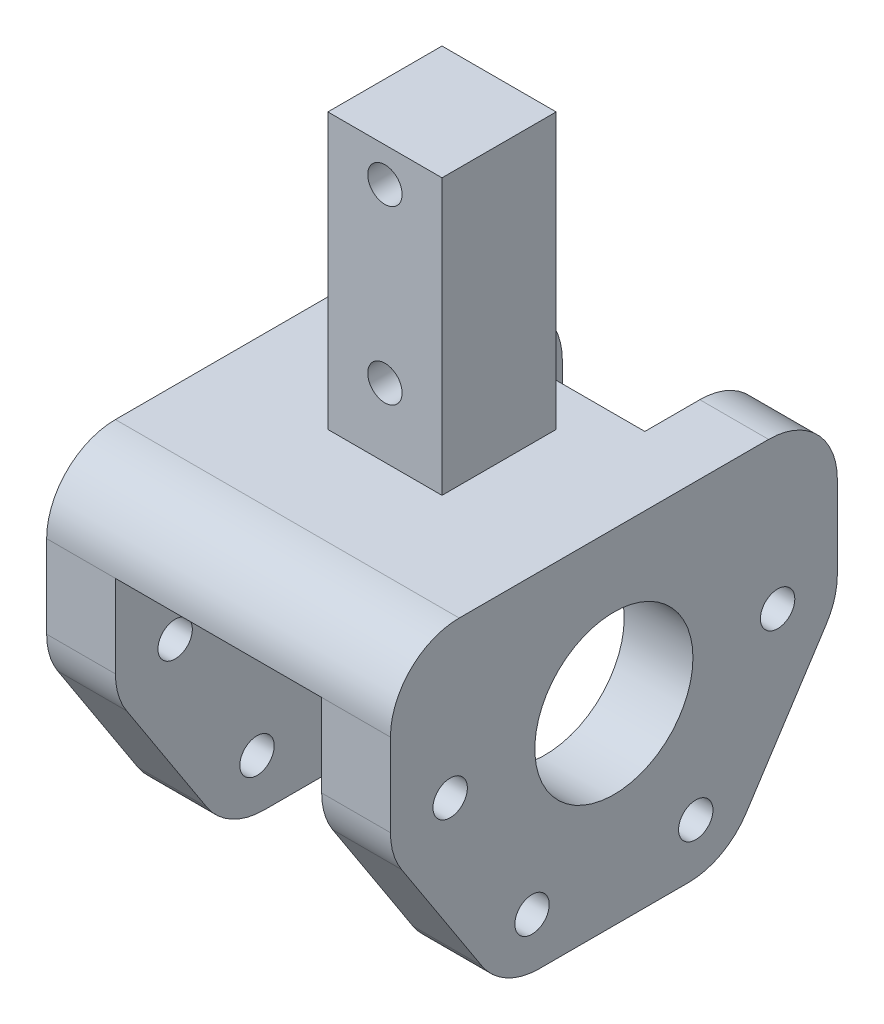
SolidWorks part; units mm, degrees
material "Nylon - impressão"
ref_plane "Plano frontal" through (0, 0, 0) normal (0, 0, 1) x (1, 0, 0)
ref_plane "Plano superior" through (0, 0, 0) normal (0, 1, 0) x (1, 0, 0)
ref_plane "Plano direito" through (0, 0, 0) normal (1, 0, 0) x (0, 0, -1)
sketch "Esboço1" plane through (0, 0, 0) normal (0, 1, 0) x (1, 0, 0)
  line L1 (-8.3, -8.3) -> (8.3, -8.3)
  line L2 (-8.3, -8.3) -> (-8.3, 8.3)
  line L3 (-8.3, 8.3) -> (8.3, 8.3)
  line L4 (8.3, -8.3) -> (8.3, 8.3)
  line L5 (-8.3, -8.3) -> (8.3, 8.3) construction
  line L6 (-8.3, 8.3) -> (8.3, -8.3) construction
  point P0 (0, 0)
  dimension "D1" = 16.6
extrude "Ressalto-extrusão1" add sketch "Esboço1" along normal blind 40
sketch "Esboço2" plane through (0, 0, 0) normal (0, -1, 0) x (1, 0, 0)
  line L1 (-25, -32.5) -> (25, -32.5)
  line L2 (-25, -32.5) -> (-25, 32.5)
  line L3 (-25, 32.5) -> (25, 32.5)
  line L4 (25, -32.5) -> (25, 32.5)
  line L5 (-25, -32.5) -> (25, 32.5) construction
  line L6 (-25, 32.5) -> (25, -32.5) construction
  point P0 (0, 0)
  dimension "D1" = 65
  dimension "D2" = 50
extrude "Ressalto-extrusão2" add sketch "Esboço2" along normal blind 50
sketch "Esboço3" plane through (0, 0, 32.5) normal (0, 0, 1) x (1, 0, 0)
  line L0 (25, -50) -> (-25, -50) construction
  line L1 (-15, -50) -> (15, -50)
  line L2 (-15, -50) -> (-15, -10)
  line L3 (-15, -10) -> (15, -10)
  line L4 (15, -50) -> (15, -10)
  line L5 (-25, -50) -> (-25, 0) construction
  line L6 (25, 0) -> (-25, 0) construction
  line L7 (25, -50) -> (25, 0) construction
  dimension "D1" = 10
  dimension "D2" = 10
  dimension "D3" = 10
extrude "Corte-extrusão1" cut sketch "Esboço3" against normal through all
sketch "Esboço4" plane through (25, 0, 0) normal (1, 0, 0) x (0, 0, -1)
  line L0 (32.5, -50) -> (-32.5, -50) construction
  line L1 (32.5, -50) -> (32.5, 0) construction
  circle A3 centre (0, -22) radius 11.5
  circle A10 centre (-23.8125, -22) radius 2.5
  circle A13 centre (23.8125, -22) radius 2.5
  circle A16 centre (0, -22) radius 23.8125 construction
  arc A17 (-9.4071, -1.4434) -> (-11.8406, -3.8769) centre (-11.9062, -1.3778) ccw [skipped]
  arc A18 (11.8464, -3.8771) -> (13.5071, -3.298) centre (11.9063, -1.3778) ccw [skipped]
  circle A19 centre (-11.9062, -42.6222) radius 2.5
  arc A20 (-11.8406, -45.1214) -> (-14.4054, -42.5566) centre (-11.9062, -42.6222) ccw [skipped]
  arc A21 (11.8345, -45.1212) -> (10.2346, -44.4811) centre (11.9063, -42.6222) ccw [skipped]
  circle A22 centre (11.9063, -42.6222) radius 2.5
  circle A23 centre (23.8125, -22) radius 2.5 construction
  circle A24 centre (11.9063, -1.3778) radius 2.5 construction
  circle A25 centre (-11.9062, -1.3778) radius 2.5 construction
  point P9 (27.1018, 14.7565)
  point P10 (27.2707, -10.0658)
  point P11 (23.6813, -19.5034)
  point P21 (0, -22)
  point P22 (0, -22)
  point P38 (0, -22)
  dimension "D2" = 47.625
  dimension "D4" = 5
  dimension "D5" = 23
  dimension "D1" = 28
  dimension "D3" = 32.5
  dimension "D6" = 6
  dimension "D7" = 6
extrude "Corte-extrusão2" cut sketch "Esboço4" against normal through all
sketch "Esboço5" plane through (-25, 0, 0) normal (-1, 0, 0) x (0, 0, 1)
  line L0 (0, 0) -> (0, -9.2798) construction
  line L1 (32.5, 0) -> (-32.5, 0) construction
  line L3 (-14.5, -5) -> (-14.5, 0)
  line L4 (-14.5, 0) -> (-32.5, 0)
  line L5 (-32.5, 0) -> (-32.5, -5)
  line L6 (-32.5, -50) -> (-32.5, 0) construction
  line L7 (-32.5, -5) -> (-14.5, -5)
  line M5 (32.5, 0) -> (-32.5, 0)
  line M6 (-32.5, 0) -> (-32.5, -50)
  dimension "D1" = 18
  dimension "D2" = 5
extrude "Corte-extrusão3" cut sketch "Esboço5" against normal up to surface (10 mm away) contours L7 L3 M5 M6 region at (-25, -2.5, -23.5) up to face at (-15, -24.5, 23.8125)
sketch "Esboço8" plane through (-15, 0, 0) normal (-1, 0, 0) x (0, 0, 1)
  line L0 (-14.5, -5) -> (-14.5, 0) construction
  line L5 (-32.5, 0) -> (-14.5, 0)
  line L6 (-32.5, 0) -> (-32.5, -10)
  line L7 (-32.5, -10) -> (-14.5, -10)
  line L8 (-14.5, 0) -> (-14.5, -10)
  line M1 (-14.5, 0) -> (-32.5, 0)
  line M3 (-32.5, -5) -> (-14.5, -5)
  line M4 (-14.5, -5) -> (-14.5, 0)
  line M5 (-32.5, 0) -> (-32.5, -5)
chamfer "Chanfro1" distance 25 angle 33 4 edges at (-20, -50, -32.5) (-20, -50, 32.5) (20, -50, 32.5) (20, -50, -32.5) first distance on face at (-3, -23, -32.5) first distance on face at (0, -27.5, 32.5)
fillet "Filete2" radius 10 10 edges at (20, -25, -32.5) (20, -50, 16.2648) (20, -50, -16.2648) (20, -25, 32.5) (0, 0, 32.5) (-20, -50, -16.2648) (-20, -50, 16.2648) (-20, -25, 32.5) (-20, -25, -32.5) (-20, -5, -32.5)
extrude "Corte-extrusão5" cut sketch "Esboço8" against normal up to surface (30 mm away) contours M1 M5 M3 M4 | L8 L6 L7 M3 region at (-15, -2.5, -23.5) region at (-15, -7.5, -23.5) up to face at (15, -19.5, 23.8125)
fillet "Filete4" radius 10 1 edges at (20, 0, -32.5)
sketch "Esboço9" plane through (0, 0, 8.3) normal (0, 0, -1) x (-1, 0, 0)
  line L1 (-15, 0) -> (25, 0) construction
  circle A0 centre (0, 10) radius 2.5
  circle A1 centre (0, 35) radius 2.5
  dimension "D2" = 25
  dimension "D3" = 5
  dimension "D1" = 10
extrude "Corte-extrusão7" cut sketch "Esboço9" along normal through all contours A0 | A1
